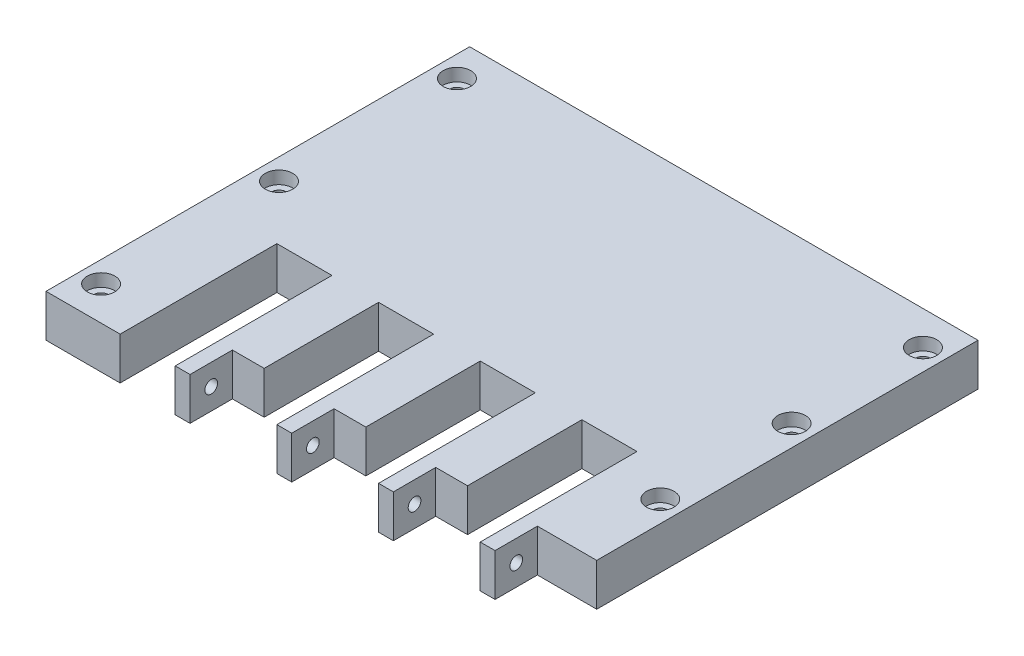
SolidWorks part; units mm, degrees
material "Plain Carbon Steel"
ref_plane "Front Plane" through (0, 0, 0) normal (0, 0, 1) x (1, 0, 0)
ref_plane "Top Plane" through (0, 0, 0) normal (0, 1, 0) x (1, 0, 0)
ref_plane "Right Plane" through (0, 0, 0) normal (1, 0, 0) x (0, 0, -1)
sketch "Sketch1" plane through (0, 0, 0) normal (0, 1, 0) x (1, 0, 0)
  line L1 (60, -50) -> (-60, -50)
  line L2 (60, -50) -> (60, 50)
  line L3 (60, 50) -> (-60, 50)
  line L4 (-60, -50) -> (-60, 50)
  line L5 (60, -50) -> (-60, 50) construction
  line L6 (60, 50) -> (-60, -50) construction
  point P0 (0, 0)
  dimension "D1" = 120
  dimension "D2" = 100
extrude "Boss-Extrude1" add sketch "Sketch1" along normal blind 10 contours L3 L1 | L3 L4 L1 | L3 L1 L2 region at (0, 0, 0)
sketch "Sketch2" plane through (0, 0, 50) normal (0, 0, 1) x (1, 0, 0)
  line L0 (-60, 0) -> (60, 0) construction
  line L1 (60, 10) -> (-60, 10) construction
  line L4 (-29.5, -10) -> (-42.5, -10)
  line L5 (-29.5, -10) -> (-29.5, 10)
  line L6 (-29.5, 10) -> (-42.5, 10)
  line L7 (-42.5, -10) -> (-42.5, 10)
  line L8 (-29.5, -10) -> (-42.5, 10) construction
  line L9 (-29.5, 10) -> (-42.5, -10) construction
  line L10 (-5.5, -10) -> (-18.5, -10)
  line L11 (-5.5, -10) -> (-5.5, 10)
  line L12 (-5.5, 10) -> (-18.5, 10)
  line L13 (-18.5, -10) -> (-18.5, 10)
  line L14 (-5.5, -10) -> (-18.5, 10) construction
  line L15 (-5.5, 10) -> (-18.5, -10) construction
  line L16 (18.5, -10) -> (5.5, -10)
  line L17 (18.5, -10) -> (18.5, 10)
  line L18 (18.5, 10) -> (5.5, 10)
  line L19 (5.5, -10) -> (5.5, 10)
  line L20 (18.5, -10) -> (5.5, 10) construction
  line L21 (18.5, 10) -> (5.5, -10) construction
  line L22 (42.5, -10) -> (29.5, -10)
  line L23 (42.5, -10) -> (42.5, 10)
  line L24 (42.5, 10) -> (29.5, 10)
  line L25 (29.5, -10) -> (29.5, 10)
  line L26 (42.5, -10) -> (29.5, 10) construction
  line L27 (42.5, 10) -> (29.5, -10) construction
  line L29 (60, 0) -> (-60, 0) construction
  point P7 (-36, 0)
  point P8 (-12, 0)
  point P9 (12, 0)
  point P10 (36, 0)
  point P11 (-36, 0)
  point P16 (-12, 0)
  point P21 (12, 0)
  point P26 (36, 0)
  point P33 (0, 0)
  dimension "D1" = 120
  dimension "D3" = 13
extrude "Cut-Extrude1" cut sketch "Sketch2" against normal blind 37
sketch "Sketch3" plane through (0, 0, 50) normal (0, 0, 1) x (1, 0, 0)
  line L0 (60, 10) -> (60, 0) construction
  line L1 (-18.5, 0) -> (-26, 0)
  line L2 (-18.5, 0) -> (-18.5, 10)
  line L3 (-18.5, 10) -> (-26, 10)
  line L4 (-26, 0) -> (-26, 10)
  line L5 (5.5, 0) -> (-2, 0)
  line L6 (5.5, 0) -> (5.5, 10)
  line L7 (5.5, 10) -> (-2, 10)
  line L8 (-2, 0) -> (-2, 10)
  line L9 (29.5, 0) -> (22, 0)
  line L10 (29.5, 0) -> (29.5, 10)
  line L11 (29.5, 10) -> (22, 10)
  line L12 (22, 0) -> (22, 10)
  line L13 (46, 0) -> (60, 0)
  line L14 (46, 0) -> (46, 10)
  line L15 (46, 10) -> (60, 10)
  line L16 (60, 0) -> (60, 10)
  line L17 (60, 0) -> (42.5, 0) construction
  line L18 (5.5, 10) -> (5.5, 0) construction
  line L19 (5.5, 0) -> (-5.5, 0) construction
  line L21 (-29.5, 0) -> (-29.5, 10) construction
  line L22 (-5.5, 0) -> (-5.5, 10) construction
  line L23 (42.5, 0) -> (42.5, 10) construction
  line L24 (18.5, 0) -> (18.5, 10) construction
  line L25 (-18.5, 0) -> (-5.5, 0) construction
  line L26 (-18.5, 10) -> (-18.5, 0) construction
  line L29 (-18.5, 10) -> (-29.5, 10) construction
  line L33 (5.5, 10) -> (-5.5, 10) construction
  line L34 (29.5, 10) -> (18.5, 10) construction
  line L35 (60, 10) -> (42.5, 10) construction
  dimension "D1" = 3.5
  dimension "D2" = 3.5
  dimension "D3" = 3.5
  dimension "D4" = 3.5
extrude "Cut-Extrude2" cut sketch "Sketch3" against normal blind 10
sketch "Sketch4" plane through (46, 0, 0) normal (1, 0, 0) x (0, 0, -1)
  line L1 (-40, 0) -> (-50, 0) construction
  line L2 (-50, 10) -> (-50, 0) construction
  circle A0 centre (-45, 5) radius 1.5
  dimension "D1" = 3
  dimension "D2" = 5
  dimension "D3" = 5
extrude "Cut-Extrude3" cut sketch "Sketch4" against normal up to surface (75.5 mm away) up to face at (-29.5, 5, 31.5)
hole_wizard "CBORE for M3 SHCS" positions "Sketch7" profile "Sketch8" counterbore size "M3" standard "ANSI Metric"
sketch "Sketch7" plane through (-676.2935, 10, -1323.2827) normal (0, 1, 0) x (1, 0, 0)
  line L3 (621.2935, -1281.2827) -> (621.2935, -1365.2827) construction
  line L5 (731.2935, -1281.2827) -> (731.2935, -1343.2827) construction
  circle A0 centre (731.2935, -1281.2827) radius 2.243
  circle A1 centre (731.2935, -1343.2827) radius 2.2384
  circle A3 centre (621.2935, -1281.2827) radius 2.3325
  circle A4 centre (621.2935, -1365.2827) radius 1.7576
  circle A5 centre (621.2935, -1323.2827) radius 1.8624
  circle A6 centre (731.2935, -1312.2827) radius 2.0271
  point P1 (731.2935, -1281.2827)
  point P8 (731.2935, -1343.2827)
  point P15 (621.2935, -1281.2827)
  point P17 (621.2935, -1365.2827)
  point P19 (621.2935, -1323.2827)
  point P27 (731.2935, -1312.2827)
sketch "Sketch8" plane through (55, 10, -42) normal (1, 0, 0) x (0, 0, 1)
  line L0 (0, 0) -> (0, 24.0215)
  line L1 (0, 24.0215) -> (1.7, 23)
  line L2 (1.7, 23) -> (1.7, 3)
  line L3 (1.7, 3) -> (3.25, 3)
  line L4 (3.25, 3) -> (3.25, 0)
  line L5 (3.25, 0) -> (0, 0)
  line L6 (0, 24.0215) -> (-1.7, 23) construction
  line L7 (0, -6.35) -> (0, 107.95) construction
  dimension "Hole Dia." = 3.4
  dimension "Hole Depth" = 23
  dimension "C'Bore Dia." = 6.5
  dimension "C'Bore Depth" = 3
  dimension "Drill Angle" = 118
